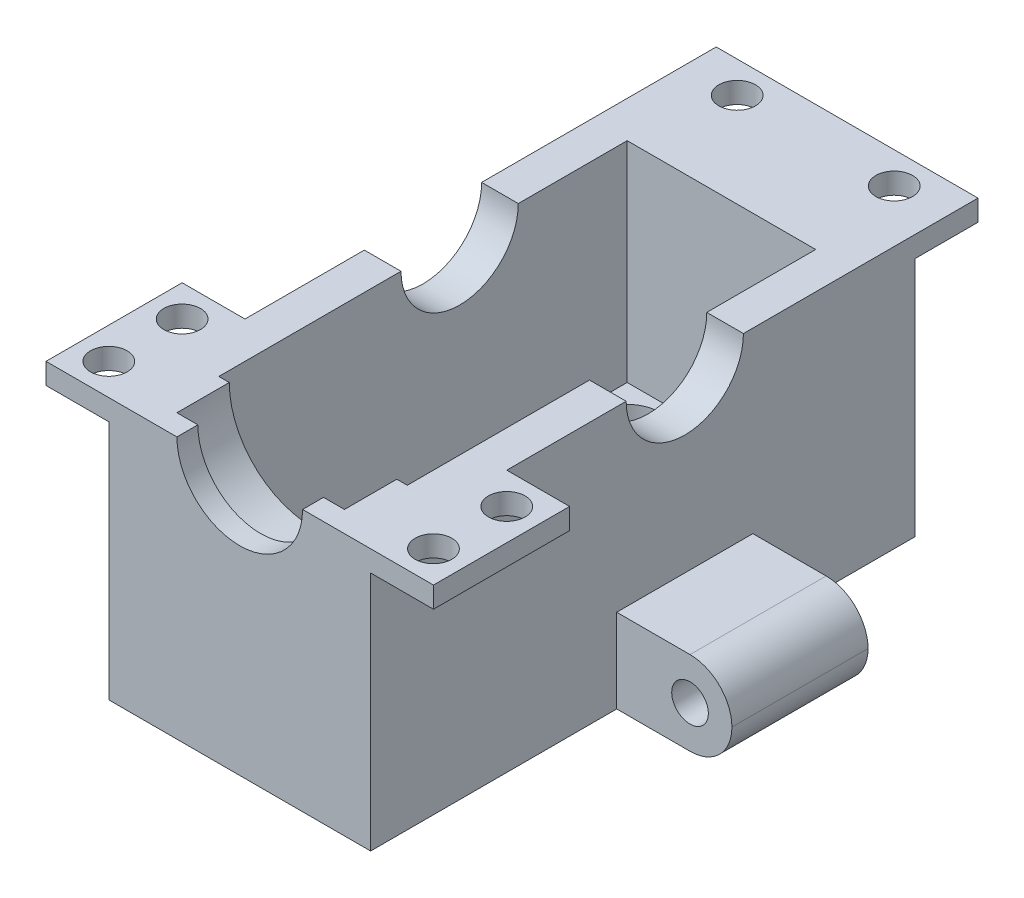
SolidWorks part; units mm, degrees
ref_plane "Alzado" through (0, 0, 0) normal (0, 0, 1) x (1, 0, 0)
ref_plane "Planta" through (0, 0, 0) normal (0, 1, 0) x (1, 0, 0)
ref_plane "Vista lateral" through (0, 0, 0) normal (1, 0, 0) x (0, 0, -1)
sketch "Croquis2" plane through (0, 0, 0) normal (0, 1, 0) x (1, 0, 0)
  line L1 (-12.5, -25) -> (12.5, -25)
  line L2 (-12.5, -25) -> (-12.5, 25)
  line L3 (-12.5, 25) -> (12.5, 25)
  line L4 (12.5, -25) -> (12.5, 25)
  line L5 (-12.5, -25) -> (12.5, 25) construction
  line L6 (-12.5, 25) -> (12.5, -25) construction
  point P0 (0, 0)
  dimension "D1" = 25
  dimension "D2" = 50
extrude "Saliente-Extruir2" add sketch "Croquis2" along normal blind 25
sketch "Croquis21" plane through (0, 0, 25) normal (0, 0, 1) x (1, 0, 0)
  line L1 (-12.5, 25) -> (12.5, 25)
  line L2 (-12.5, 25) -> (-12.5, 0)
  line L3 (-12.5, 0) -> (12.5, 0)
  line L4 (12.5, 25) -> (12.5, 0)
extrude "Saliente-Extruir11" add sketch "Croquis21" along normal blind 6
sketch "Croquis4" plane through (0, 0, 0) normal (1, 0, 0) x (0, 0, -1)
  line L0 (-31, 25) -> (25, 25) construction
  line L1 (-26, 25) -> (13, 25)
  line L2 (13, 5) -> (-26, 5)
  line L3 (-26, 5) -> (-26, 25)
  line L4 (25, 0) -> (-31, 0) construction
  line L5 (13, 25) -> (13, 5)
  dimension "D1" = 12
  dimension "D2" = 5
extrude "Cortar-Extruir1" cut sketch "Croquis4" against normal mid plane 18 contours L5 | L5 region at (0, 15, 6.5)
sketch "Croquis5" plane through (0, 0, 0) normal (1, 0, 0) x (0, 0, -1)
  line L0 (-31, 25) -> (25, 25) construction
  line L1 (-8.6, 25) -> (2.6, 25)
  circle A0 centre (-3, 25) radius 5.6
  dimension "D1" = 11.2
extrude "Cortar-Extruir2" cut sketch "Croquis5" against normal through all both and the other way through all contours L1 A0 region at (0, 22.6233, 3)
sketch "Croquis9" plane through (0, 0, 31) normal (0, 0, 1) x (1, 0, 0)
  line L0 (0, 25) -> (0, 0) construction
  line L2 (12.5, 25) -> (-12.5, 25) construction
  circle A0 centre (0, 25) radius 8
  dimension "D1" = 16
extrude "Cortar-Extruir3" cut sketch "Croquis9" against normal blind 5
sketch "Croquis23" plane through (0, 0, 31) normal (0, 0, 1) x (1, 0, 0)
  line L0 (-9, 25) -> (9, 25) construction
  line L5 (6, 25) -> (12.5, 25)
  line L6 (-12.5, 0) -> (12.5, 0)
  line L7 (-12.5, 0) -> (-12.5, 25)
  line L8 (-12.5, 25) -> (-6, 25)
  line L9 (12.5, 0) -> (12.5, 25)
  arc A1 (-6, 25) -> (6, 25) centre (0, 25) ccw
  arc M1 (8, 25) -> (-8, 25) centre (0, 25) cw
  line M2 (-8, 25) -> (-12.5, 25)
  line M3 (-12.5, 25) -> (-12.5, 0)
  line M4 (-12.5, 0) -> (12.5, 0)
  line M5 (12.5, 0) -> (12.5, 25)
  line M6 (12.5, 25) -> (8, 25)
  dimension "D1" = 12
extrude "Saliente-Extruir12" add sketch "Croquis23" along normal blind 2 contours M6 M1 M2 M3 M4 M5 | A1 L8 M1 | L7 L6 L9 L8 | A1 region at (7, 24.8211, 31) region at (0, 10.7548, 31)
sketch "Croquis11" plane through (12.5, 0, 0) normal (1, 0, 0) x (0, 0, -1)
  line L1 (-33, 25) -> (-20, 25)
  line L2 (-33, 25) -> (-33, 23)
  line L3 (-33, 23) -> (-20, 23)
  line L4 (-20, 25) -> (-20, 23)
  line L5 (-33, 25) -> (-8.6, 25) construction
  dimension "D2" = 2
  dimension "D3" = 13
extrude "Saliente-Extruir4" add sketch "Croquis11" along normal blind 6
sketch "Croquis12" plane through (0, 25, 0) normal (0, 1, 0) x (1, 0, 0)
  line L0 (18.5, -20) -> (18.5, -33) construction
  line L1 (18.5, -20) -> (12.5, -20) construction
  line L3 (18.5, -33) -> (6, -33) construction
  line L4 (18.5, -20) -> (18.5, -33) construction
  circle A0 centre (15.5, -23) radius 1.75
  circle A1 centre (15.5, -30) radius 1.75
  dimension "D1" = 3.5
  dimension "D3" = 3.5
  dimension "D5" = 3
  dimension "D6" = 3
  dimension "D4" = 3
  dimension "D2" = 3
extrude "Cortar-Extruir4" cut sketch "Croquis12" against normal through all
sketch "Croquis13" plane through (-12.5, 0, 0) normal (-1, 0, 0) x (0, 0, 1)
  line L1 (33, 25) -> (20, 25)
  line L2 (33, 25) -> (33, 23)
  line L3 (33, 23) -> (20, 23)
  line L4 (20, 25) -> (20, 23)
  line L5 (8.6, 25) -> (33, 25) construction
  dimension "D1" = 2
  dimension "D3" = 13
extrude "Saliente-Extruir5" add sketch "Croquis13" along normal blind 6
sketch "Croquis14" plane through (0, 25, 0) normal (0, 1, 0) x (1, 0, 0)
  line L1 (-18.5, -33) -> (-18.5, -20) construction
  line L2 (-18.5, -20) -> (-12.5, -20) construction
  line L3 (-18.5, -33) -> (-18.5, -20) construction
  line L4 (-18.5, -33) -> (-6, -33) construction
  circle A0 centre (-15.5, -23) radius 1.75
  circle A1 centre (-15.5, -30) radius 1.75
  dimension "D1" = 3.5
  dimension "D2" = 3.5
  dimension "D6" = 3
  dimension "D4" = 3
  dimension "D3" = 3
  dimension "D5" = 3
extrude "Cortar-Extruir5" cut sketch "Croquis14" against normal through all
sketch "Croquis16" plane through (0, 25, 0) normal (0, 1, 0) x (1, 0, 0)
  line L1 (12.5, 2.6) -> (12.5, 25) construction
  line L2 (-12.5, 25) -> (-12.5, 2.6) construction
  line L3 (12.5, 25) -> (-12.5, 25) construction
  circle A0 centre (-7.5, 22) radius 1.75
  circle A1 centre (7.5, 22) radius 1.75
  dimension "D5" = 3.5
  dimension "D6" = 3.5
  dimension "D1" = 3
  dimension "D2" = 3
  dimension "D3" = 5
  dimension "D4" = 5
extrude "Cortar-Extruir6" cut sketch "Croquis16" against normal through all
sketch "Croquis24" plane through (0, 5, 0) normal (0, 1, 0) x (1, 0, 0)
  line L1 (-9, -26) -> (9, -26) construction
  line L2 (-9, 13) -> (9, 13) construction
  line L4 (-9, -26) -> (-9, -8.6) construction
  line L5 (9, 13) -> (9, -26) construction
  line L6 (-9, 2.6) -> (-9, 13) construction
  line L7 (-9, 13) -> (9, 13) construction
  circle A0 centre (-5, -22) radius 1.75
  circle A1 centre (-5, 9) radius 1.75
  circle A2 centre (5, -22) radius 1.75
  circle A3 centre (5, 9) radius 1.75
  dimension "D1" = 3.5
  dimension "D2" = 3.5
  dimension "D7" = 3.5
  dimension "D8" = 3.5
  dimension "D9" = 4
  dimension "D3" = 4
  dimension "D4" = 4
  dimension "D10" = 4
  dimension "D11" = 4
  dimension "D12" = 4
  dimension "D5" = 4
  dimension "D6" = 4
extrude "Cortar-Extruir8" cut sketch "Croquis24" against normal through all
sketch "Croquis25" plane through (0, 0, -25) normal (0, 0, -1) x (-1, 0, 0)
  line L0 (12.5, 25) -> (12.5, 0) construction
  line L1 (-12.5, 23) -> (12.5, 23)
  line L2 (-12.5, 23) -> (-12.5, 0)
  line L3 (-12.5, 0) -> (12.5, 0)
  line L4 (12.5, 23) -> (12.5, 0)
  line L5 (-12.5, 25) -> (12.5, 25) construction
  dimension "D1" = 2
extrude "Cortar-Extruir9" cut sketch "Croquis25" against normal blind 6
sketch "Croquis28" plane through (12.5, 0, 0) normal (1, 0, 0) x (0, 0, -1)
  line L0 (-33, 0) -> (19, 0) construction
  line L1 (-9.5, 0) -> (3.5, 0)
  line L2 (-9.5, 0) -> (-9.5, 8)
  line L3 (-9.5, 8) -> (3.5, 8)
  line L4 (3.5, 0) -> (3.5, 8)
  line L5 (-3, 25) -> (-3, 0) construction
  dimension "D1" = 13
  dimension "D2" = 8
extrude "Saliente-Extruir13" add sketch "Croquis28" along normal blind 11
fillet "Redondeo1" radius 4 2 edges at (23.5, 0, 3) (23.5, 8, 3)
sketch "Croquis29" plane through (0, 0, -3.5) normal (0, 0, -1) x (-1, 0, 0)
  circle A0 centre (-19.5, 4) radius 1.75
  dimension "D1" = 3.5
extrude "Cortar-Extruir10" cut sketch "Croquis29" against normal through all
ref_plane "Plano1" through (0, 0, 0) normal (-1, 0, 0) x (0, 0, 1)
mirror "Simetría1" about plane through (0, 0, 0) normal (-1, 0, 0) of "Redondeo1", "Cortar-Extruir10", "Saliente-Extruir13"
sketch "Croquis30" plane through (0, 5, 0) normal (0, 1, 0) x (1, 0, 0)
  circle A0 centre (-5, 9) radius 3.1
  circle A1 centre (-5, -22) radius 3.1
  circle A2 centre (5, -22) radius 3.1
  circle A3 centre (5, 9) radius 3.1
  dimension "D1" = 6.2
  dimension "D2" = 6.2
  dimension "D3" = 6.2
  dimension "D4" = 6.2
extrude "Cortar-Extruir11" cut sketch "Croquis30" against normal blind 3
